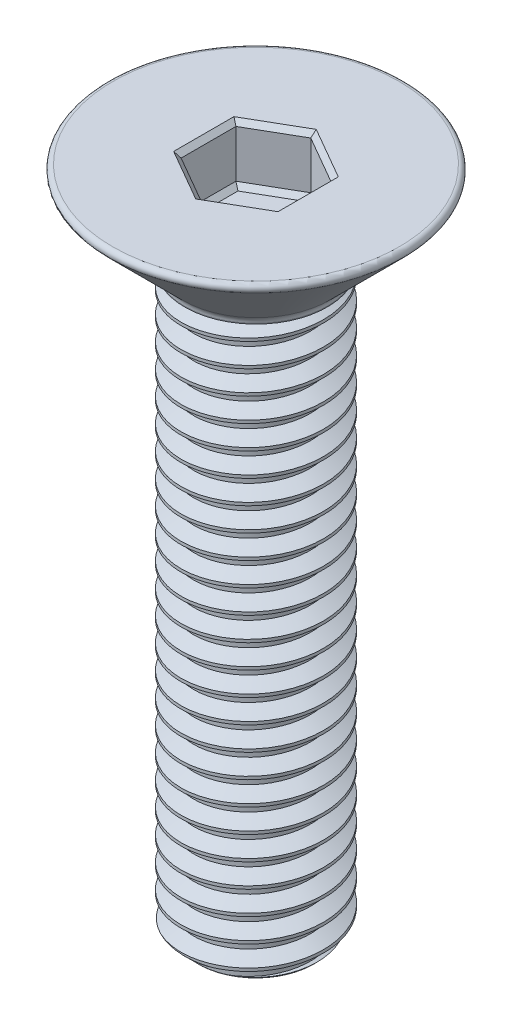
SolidWorks part; units mm, degrees
material "AISI Type A2 Tool Steel"
ref_plane "Front Plane" through (0, 0, 0) normal (0, 0, 1) x (1, 0, 0)
ref_plane "Top Plane" through (0, 0, 0) normal (0, 1, 0) x (1, 0, 0)
ref_plane "Right Plane" through (0, 0, 0) normal (1, 0, 0) x (0, 0, -1)
sketch "Sketch1" plane through (0, 0, 0) normal (0, 1, 0) x (1, 0, 0)
  circle A0 centre (0, 0) radius 1.5
  dimension "D1" = 3
extrude "Boss-Extrude1" add sketch "Sketch1" along normal blind 12.14
thread "Thread1" pitch 0.5 method cut profile "Thread Profile1" start angle 0, offset 1, length 0, pitch 0.5, diameter 3
ref_plane "Plane1" through (-1.5, 13.14, 0) normal (0, 0, 1) x (-1, 0, 0)
sketch "Thread Profile1" plane through (-1.5, 13.14, 0) normal (0, 0, 1) x (-1, 0, 0)
  line L0 (0, 0) -> (0, 0.5) construction
  line L11 (0, 0) -> (0, 0.4375)
  line L12 (0, 0.4375) -> (-0.2706, 0.2812)
  line L13 (-0.2706, 0.2812) -> (-0.2706, 0.1562)
  line L15 (-0.2706, 0.1562) -> (0, 0)
  line L17 (-0.2706, 0.2187) -> (0, 0.2187) construction
  point P2 (0, 0)
  dimension "Pitch" = 0.5
  dimension "Profile_Angle" = 60
  dimension "Profile_Land" = 0.125
  dimension "Profile_Height" = 0.2706
sketch "Sketch5" plane through (0, 12.14, 0) normal (0, 1, 0) x (1, 0, 0)
  circle A0 centre (0, 0) radius 1.5
  dimension "D1" = 3
extrude "Boss-Extrude2" add sketch "Sketch5" along normal blind 0.1
sketch "Sketch6" plane through (0, 12.24, 0) normal (0, 1, 0) x (1, 0, 0)
  circle A0 centre (0, 0) radius 1.5
  dimension "D1" = 3
extrude "Boss-Extrude3" add sketch "Sketch6" along normal blind 1.76 draft 45 draft outward yes
sketch "Sketch7" plane through (0, 0, 0) normal (0, 0, 1) x (1, 0, 0)
  line L0 (0, 0) -> (0, 0.1997) construction
  line L1 (0, 0) -> (1.51, 0) construction
  line L2 (1.51, 0) -> (1.51, 0.3)
  line L3 (1.51, 0.3) -> (1.21, 0)
  line L4 (1.21, 0) -> (1.51, 0)
  dimension "D1" = 45
  dimension "D2" = 0.3
  dimension "D3" = 1.51
revolve "Cut-Revolve1" cut sketch "Sketch7" angle 360 about L0
fillet "Fillet1" radius 0.1 1 edges at (0, 14, 3.26)
fillet "Fillet2" radius 0.2 1 edges at (0, 12.24, 1.5)
sketch "Sketch8" plane through (0, 14, 0) normal (0, 1, 0) x (1, 0, 0)
  line L1 (0, 1.1547) -> (-1, 0.5774)
  line L2 (-1, 0.5774) -> (-1, -0.5774)
  line L3 (-1, -0.5774) -> (0, -1.1547)
  line L4 (0, -1.1547) -> (1, -0.5774)
  line L5 (1, -0.5774) -> (1, 0.5774)
  line L6 (1, 0.5774) -> (0, 1.1547)
  circle A0 centre (0, 0) radius 1 construction
  dimension "D1" = 2
extrude "Cut-Extrude1" cut sketch "Sketch8" against normal blind 1.1
chamfer "Chamfer1" distance 0.1 angle 45 6 edges at (-1, 14, 0) (-0.5, 14, 0.866) (0.5, 14, 0.866) (1, 14, 0) (0.5, 14, -0.866) (-0.5, 14, -0.866)
sketch "Sketch9" plane through (0, 12.9, 0) normal (0, 1, 0) x (1, 0, 0)
  line L1 (0, 1.1547) -> (-1, 0.5774)
  line L2 (-1, 0.5774) -> (-1, -0.5774)
  line L3 (-1, -0.5774) -> (0, -1.1547)
  line L4 (0, -1.1547) -> (1, -0.5774)
  line L5 (1, -0.5774) -> (1, 0.5774)
  line L6 (1, 0.5774) -> (0, 1.1547)
  circle A0 centre (0, 0) radius 1 construction
extrude "Cut-Extrude2" cut sketch "Sketch9" against normal blind 0.1 draft 45
sketch "Sketch10" plane through (0, 14, 0) normal (0, 1, 0) x (1, 0, 0)
  point P0 (0, 0)
